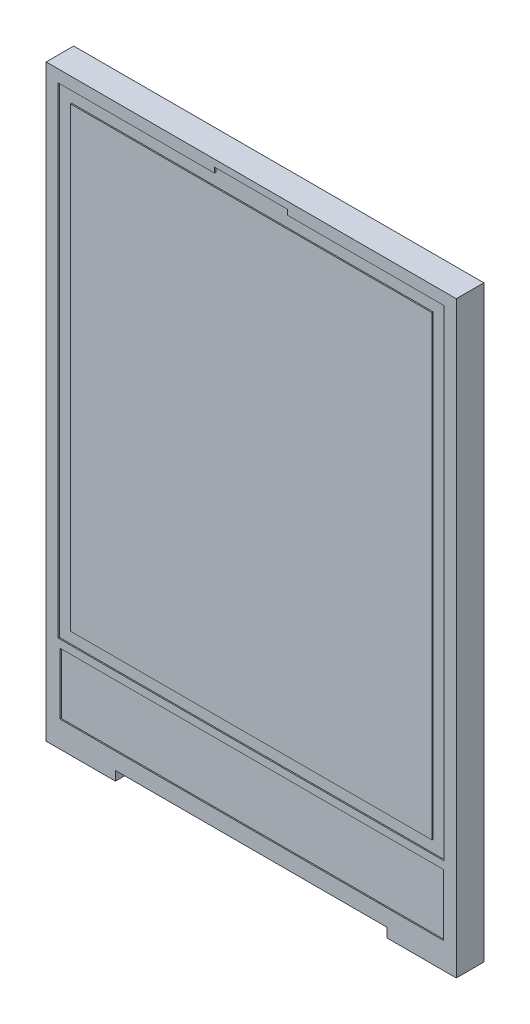
SolidWorks part; units mm, degrees
material "Plastique personnalisé"
ref_plane "Plan de face" through (0, 0, 0) normal (0, 0, 1) x (1, 0, 0)
ref_plane "Plan de dessus" through (0, 0, 0) normal (0, 1, 0) x (1, 0, 0)
ref_plane "Plan de droite" through (0, 0, 0) normal (1, 0, 0) x (0, 0, -1)
sketch "Esquisse6" plane through (0, 0, 0) normal (0, 0, 1) x (1, 0, 0)
  line L1 (0, 0) -> (35.7, 0)
  line L2 (0, 0) -> (0, 51.2)
  line L3 (0, 51.2) -> (35.7, 51.2)
  line L4 (35.7, 0) -> (35.7, 51.2)
  dimension "D1" = 51.2
  dimension "D2" = 35.7
extrude "Boss.-Extru.3" add sketch "Esquisse6" against normal blind 2.4
sketch "Esquisse7" plane through (0, 0, 0) normal (0, 0, 1) x (1, 0, 0)
  line L0 (1.0533, 51.2) -> (34.6467, 51.2) construction
  line L1 (35.7, 51.2) -> (0, 51.2) construction
  line L2 (17.85, 51.2) -> (17.85, 55.0194) construction
  line L3 (17.85, 51.2) -> (17.85, 50.15) construction
  line L4 (17.85, 50.15) -> (0, 50.15) construction
  line L5 (0, 51.2) -> (0, 0) construction
  line L6 (1.0533, 51.2) -> (1.0533, 8.3) construction
  line L7 (17.85, 50.15) -> (35.7, 50.15) construction
  line L8 (35.7, 0) -> (35.7, 51.2) construction
  line L9 (34.6467, 51.2) -> (34.6467, 8.3) construction
  line L11 (34.6467, 8.3) -> (1.0533, 8.3)
  line L12 (34.6467, 8.3) -> (34.6467, 50.15)
  line L13 (34.6467, 50.15) -> (1.0533, 50.15)
  line L14 (1.0533, 8.3) -> (1.0533, 50.15)
  dimension "D1" = 1.05
  dimension "D3" = 42.9
extrude "Enlèv. mat.-Extru.4" cut sketch "Esquisse7" against normal blind 0.1
sketch "Esquisse8" plane through (0, 0, 0) normal (0, 0, 1) x (1, 0, 0)
  line L0 (17.85, 50.15) -> (21.0264, 50.15) construction
  line L1 (34.6467, 50.15) -> (1.0533, 50.15) construction
  line L2 (21.0264, 50.15) -> (21.0264, 50.5994) construction
  line L3 (21.0264, 50.5994) -> (17.85, 50.5994) construction
  line L4 (14.6736, 50.5994) -> (21.0264, 50.5994)
  line L5 (21.0264, 50.5994) -> (21.0264, 50.15)
  line L6 (21.0264, 50.15) -> (14.6736, 50.15)
  line L7 (17.85, 50.15) -> (17.85, 51.345) construction
  line L8 (14.6736, 50.5994) -> (14.6736, 50.15)
extrude "Enlèv. mat.-Extru.5" cut sketch "Esquisse8" against normal blind 0.1
sketch "Esquisse9" plane through (0, 0, -0.1) normal (0, 0, 1) x (1, 0, 0)
  line L0 (1.0533, 50.15) -> (2.111, 50.15) construction
  line L1 (14.6736, 50.15) -> (1.0533, 50.15) construction
  line L2 (2.111, 50.15) -> (2.111, 49.1) construction
  line L3 (17.85, 50.5994) -> (17.85, 42.714) construction
  line L4 (21.0264, 50.5994) -> (14.6736, 50.5994) construction
  line L5 (34.6467, 50.15) -> (33.589, 50.15) construction
  line L6 (33.589, 50.15) -> (33.589, 49.1) construction
  line L7 (1.0533, 29.225) -> (43.4835, 29.225) construction
  line L8 (1.0533, 50.15) -> (1.0533, 8.3) construction
  line L9 (33.589, 8.3) -> (33.589, 9.35) construction
  line L10 (2.111, 8.3) -> (2.111, 9.35) construction
  line L12 (33.589, 9.35) -> (2.111, 9.35)
  line L13 (33.589, 9.35) -> (33.589, 49.1)
  line L14 (33.589, 49.1) -> (2.111, 49.1)
  line L15 (2.111, 9.35) -> (2.111, 49.1)
  point P17 (33.589, 49.625)
  dimension "D1" = 1.05
extrude "Boss.-Extru.4" add sketch "Esquisse9" along normal blind 0.1
sketch "Esquisse10" plane through (0, 0, 0) normal (0, 0, 1) x (1, 0, 0)
  line L1 (1.2288, 7.619) -> (34.6026, 7.619)
  line L2 (1.2288, 7.619) -> (1.2288, 2.2724)
  line L3 (1.2288, 2.2724) -> (34.6026, 2.2724)
  line L4 (34.6026, 7.619) -> (34.6026, 2.2724)
extrude "Enlèv. mat.-Extru.6" cut sketch "Esquisse10" against normal blind 0.1
sketch "Esquisse11" plane through (0, 0, 0) normal (0, 0, 1) x (1, 0, 0)
  line L0 (17.85, 0) -> (17.85, -3.551) construction
  line L1 (0, 0) -> (35.7, 0) construction
  line L2 (29.6695, 0) -> (29.6695, 0.808)
  line L3 (6.0305, 0) -> (29.6695, 0)
  line L4 (6.0305, 0) -> (6.0305, 0.808)
  line L5 (6.0305, 0.808) -> (29.6695, 0.808)
  point P8 (17.85, 0.808)
extrude "Enlèv. mat.-Extru.7" cut sketch "Esquisse11" against normal through all
ref_axis "charniereecran" through (29.6695, 0.808, -2.4) along (-1, 0, 0)
sketch "Esquisse12" plane through (0, 0, -2.4) normal (0, 0, -1) x (-1, 0, 0)
  line L0 (-18.0227, 51.2) -> (-18.0227, -16.4162) construction
  line L1 (-35.7, 51.2) -> (0, 51.2) construction
ref_axis "axecentrage" through (18.0227, 51.2, -2.4) along (0, -1, 0)
